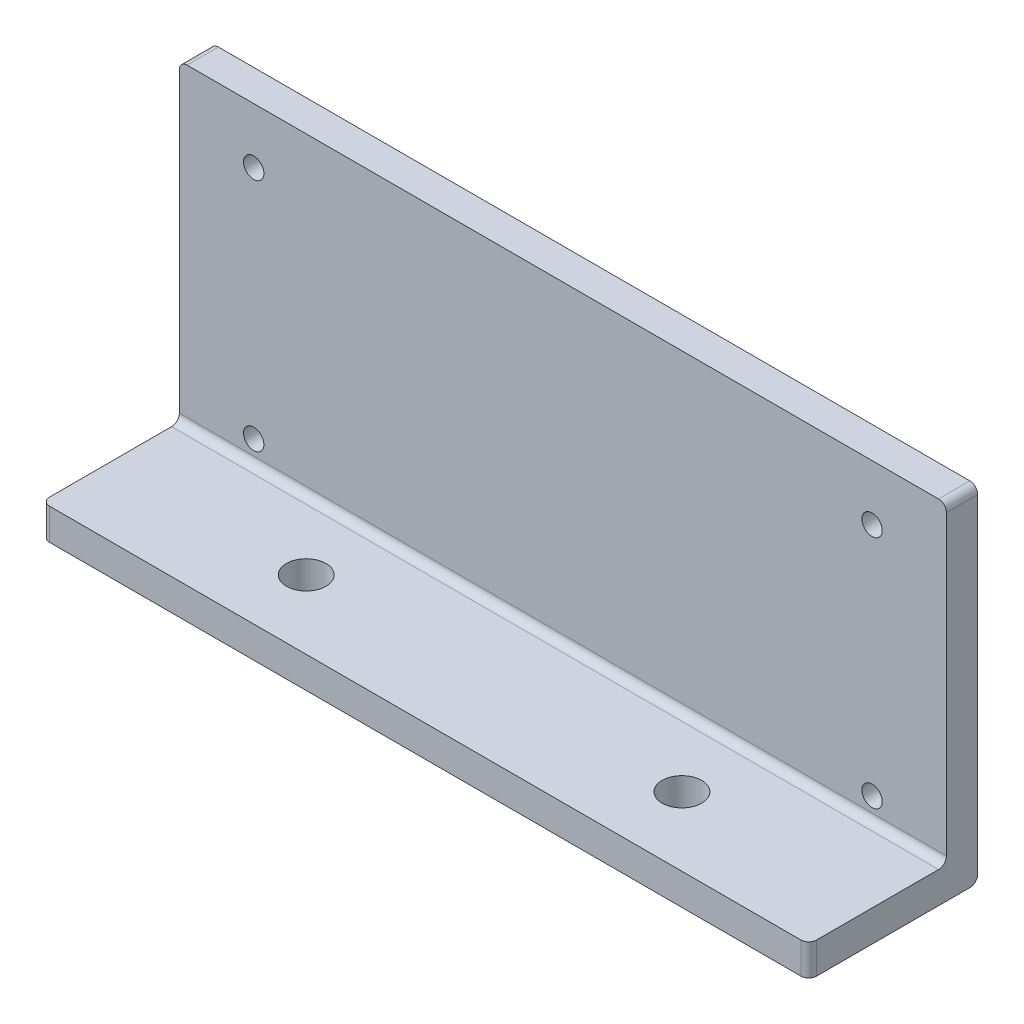
SolidWorks part; units mm, degrees
material "6061-T6 (SS)"
ref_plane "Front Plane" through (0, 0, 0) normal (0, 0, 1) x (1, 0, 0)
ref_plane "Top Plane" through (0, 0, 0) normal (0, 1, 0) x (1, 0, 0)
ref_plane "Right Plane" through (0, 0, 0) normal (1, 0, 0) x (0, 0, -1)
sketch "Sketch1" plane through (0, 0, 0) normal (0, 1, 0) x (1, 0, 0)
  line L1 (-49, -10.795) -> (49, -10.795)
  line L2 (-49, -10.795) -> (-49, 10.795)
  line L3 (-49, 10.795) -> (49, 10.795)
  line L4 (49, -10.795) -> (49, 10.795)
  line L5 (-49, -10.795) -> (49, 10.795) construction
  line L6 (-49, 10.795) -> (49, -10.795) construction
  point P0 (0, 0)
  dimension "D1" = 98
  dimension "D2" = 21.59
extrude "Boss-Extrude1" add sketch "Sketch1" along normal blind 4
sketch "Sketch2" plane through (0, 4, 0) normal (0, 1, 0) x (1, 0, 0)
  line L0 (-49, 10.795) -> (-49, -10.795) construction
  line L1 (49, 10.795) -> (-49, 10.795)
  line L2 (49, 10.795) -> (49, 6.795)
  line L3 (49, 6.795) -> (-49, 6.795)
  line L4 (-49, 10.795) -> (-49, 6.795)
  dimension "D1" = 4
extrude "Boss-Extrude2" add sketch "Sketch2" along normal blind 40
sketch "Sketch3" plane through (0, 0, -6.795) normal (0, 0, 1) x (1, 0, 0)
  line L0 (-49, 44) -> (49, 44) construction
  line L1 (-39.5, 36.9041) -> (39.5, 6.9041) construction
  line L2 (-39.5, 6.9041) -> (39.5, 36.9041) construction
  circle A0 centre (-39.5, 6.9041) radius 0.8
  circle A1 centre (-39.5, 36.9041) radius 0.8
  circle A2 centre (39.5, 36.9041) radius 0.8
  circle A3 centre (39.5, 6.9041) radius 0.8
fillet "Fillet1" radius 1 6 edges at (0, 0, -10.795) (0, 4, -6.795) (49, 2, 10.795) (-49, 44, -8.795) (49, 44, -8.795) (-49, 2, 10.795)
sketch "Sketch4" plane through (0, 4, 0) normal (0, 1, 0) x (1, 0, 0)
  line L0 (-49, -2) -> (49, -2) construction
  line L1 (-49, 5.795) -> (-49, -9.795) construction
  line L2 (49, -9.795) -> (49, 5.795) construction
  line L3 (-48, -10.795) -> (48, -10.795) construction
  line L5 (0, -11.8745) -> (0, 11.8745) construction
  circle A0 centre (-24, -2) radius 1
  circle A2 centre (24, -2) radius 1
  dimension "D1" = 25
  dimension "D2" = 8.795
hole_wizard "M2 Clearance Hole1" positions "3DSketch1" profile "Sketch5" hole size "M2" standard "ANSI Metric" end condition through all
sketch3d "3DSketch1"
  point P0 (39.5, 36.9041, -6.795)
  point P3 (39.5, 6.9041, -6.795)
  point P6 (-39.5, 36.9041, -6.795)
  point P9 (-39.5, 6.9041, -6.795)
sketch "Sketch5" plane through (39.5, 36.9041, -6.795) normal (1, 0, 0) x (0, -1, 0)
  line L0 (0, 0) -> (0, 4)
  line L1 (0, 4) -> (1.3, 4)
  line L2 (1.3, 4) -> (1.3, 0)
  line L5 (1.3, 0) -> (0, 0)
  line L11 (0, -6.35) -> (0, 107.95) construction
  dimension "Thru Hole Dia." = 2.6
  dimension "Thru Hole Depth" = 4
hole_wizard "#8 (0.199) Diameter Hole1" positions "3DSketch2" profile "Sketch6" hole size "#8" standard "ANSI Inch" end condition through all
sketch3d "3DSketch2"
  point P0 (-24, 4, 2)
  point P3 (24, 4, 2)
sketch "Sketch6" plane through (-24, 4, 2) normal (1, 0, 0) x (0, 0, 1)
  line L0 (0, 0) -> (0, 4)
  line L1 (0, 4) -> (2.5273, 4)
  line L2 (2.5273, 4) -> (2.5273, 0)
  line L5 (2.5273, 0) -> (0, 0)
  line L11 (0, -6.35) -> (0, 107.95) construction
  dimension "Thru Hole Dia." = 5.0546
  dimension "Thru Hole Depth" = 4
